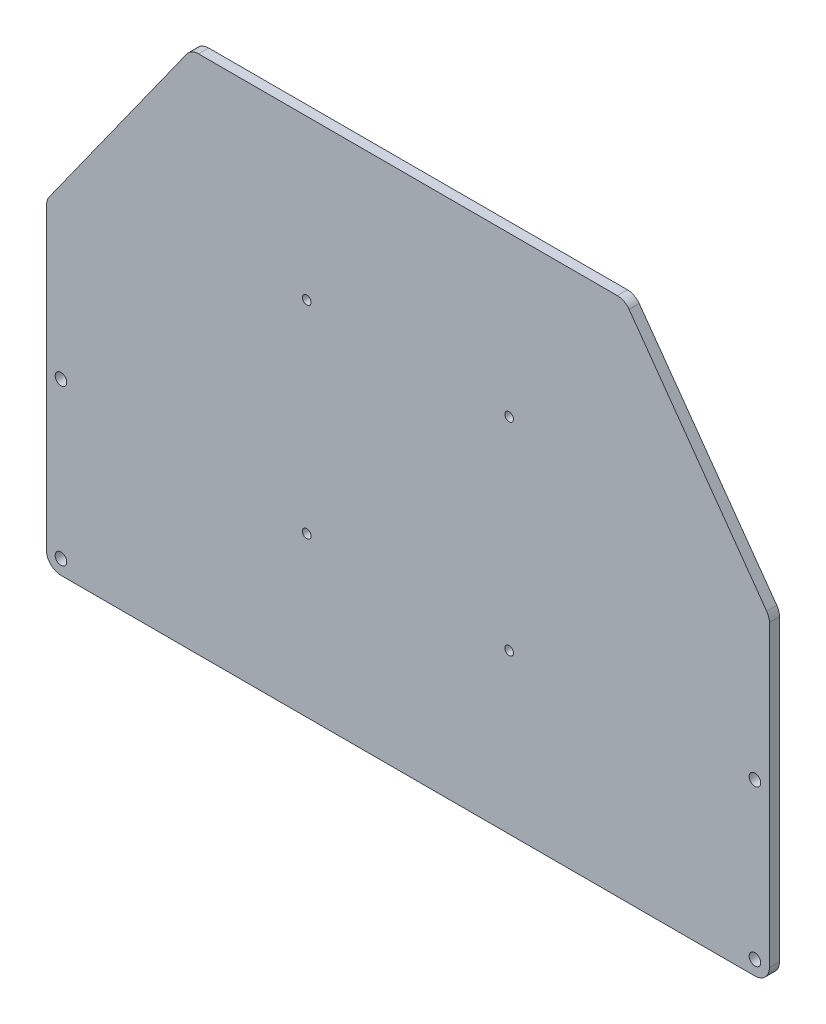
SolidWorks part; units mm, degrees
ref_plane "Plan de face" through (0, 0, 0) normal (0, 0, 1) x (1, 0, 0)
ref_plane "Plan de dessus" through (0, 0, 0) normal (0, 1, 0) x (1, 0, 0)
ref_plane "Plan de droite" through (0, 0, 0) normal (1, 0, 0) x (0, 0, -1)
sketch "Esquisse1" plane through (0, 0, 0) normal (0, 0, 1) x (1, 0, 0)
  line L1 (5, 0) -> (245, 0)
  line L2 (0, 5) -> (0, 305)
  line L3 (0, 305) -> (250, 305)
  line L4 (250, 5) -> (250, 305)
  arc A0 (250, 5) -> (245, 0) centre (245, 5) cw
  arc A1 (5, 0) -> (0, 5) centre (5, 5) cw
  point P7 (250, 0)
  point P10 (0, 0)
  dimension "D2" = 5
  dimension "D3" = 5
  dimension "D1" = 250
  dimension "D4" = 300
extrude "Boss.-Extru.1" add sketch "Esquisse1" along normal blind 3.5
sketch "Esquisse2" plane through (0, 0, 3.5) normal (0, 0, 1) x (1, 0, 0)
  line L0 (-19.0099, 5) -> (402.2953, 5) construction
  line L1 (5, 0) -> (245, 0) construction
  line L2 (5, -25.1291) -> (5, 139.966) construction
  line L3 (0, 305) -> (0, 5) construction
  line L4 (245, -22.1166) -> (245, 94.5536) construction
  line L5 (250, 5) -> (250, 305) construction
  line L6 (-9.3926, 58.8) -> (267.0784, 58.8) construction
  circle A0 centre (5, 5) radius 2
  circle A1 centre (245, 5) radius 2
  circle A2 centre (5, 58.8) radius 2
  circle A3 centre (245, 58.8) radius 2
  dimension "D1" = 4
  dimension "D2" = 4
  dimension "D7" = 4
  dimension "D8" = 4
  dimension "D3" = 5
  dimension "D4" = 5
  dimension "D5" = 5
  dimension "D6" = 53.8
extrude "Enlèv. mat.-Extru.1" cut sketch "Esquisse2" against normal through all
sketch "Esquisse3" plane through (0, 0, 3.5) normal (0, 0, 1) x (1, 0, 0)
  line L0 (0, 110) -> (50, 180)
  line L1 (50, 180) -> (200, 180)
  line L2 (200, 180) -> (250, 110)
  line L3 (125, 632.4465) -> (125, -22.4465) construction
  line L4 (250, 305) -> (0, 305) construction
  line L5 (0, 305) -> (0, 5) construction
  line L6 (250, 5) -> (250, 305) construction
  line L7 (5, 0) -> (245, 0) construction
  point P8 (125, 305)
  point P9 (125, 180)
  dimension "D1" = 110
  dimension "D2" = 110
  dimension "D3" = 150
  dimension "D4" = 180
  dimension "D5" = 180
extrude "Enlèv. mat.-Extru.2" cut sketch "Esquisse3" against normal through all and the other way through all
fillet "Congé1" radius 5 4 edges at (250, 110, 1.75) (200, 180, 1.75) (50, 180, 1.75) (0, 110, 1.75)
sketch "Esquisse4" plane through (0, 0, 0) normal (0, 0, -1) x (-1, 0, 0)
  line L0 (-125, 189.0138) -> (-125, -13.9215) construction
  line L1 (-262.4358, 90) -> (45.4804, 90) construction
  line L3 (-52.5731, 180) -> (-197.4269, 180) construction
  circle A0 centre (-160, 55) radius 1.5
  circle A1 centre (-160, 125) radius 1.5
  circle A2 centre (-90, 125) radius 1.5
  circle A3 centre (-90, 55) radius 1.5
  point P4 (0, 0)
  point P8 (-125, 180)
  dimension "D3" = 3
  dimension "D4" = 3
  dimension "D5" = 3
  dimension "D6" = 3
  dimension "D12" = 35
  dimension "D1" = 70
  dimension "D2" = 70
  dimension "D7" = 70
  dimension "D8" = 70
  dimension "D9" = 35
  dimension "D10" = 35
  dimension "D13" = 90
extrude "Enlèv. mat.-Extru.3" cut sketch "Esquisse4" against normal through all
